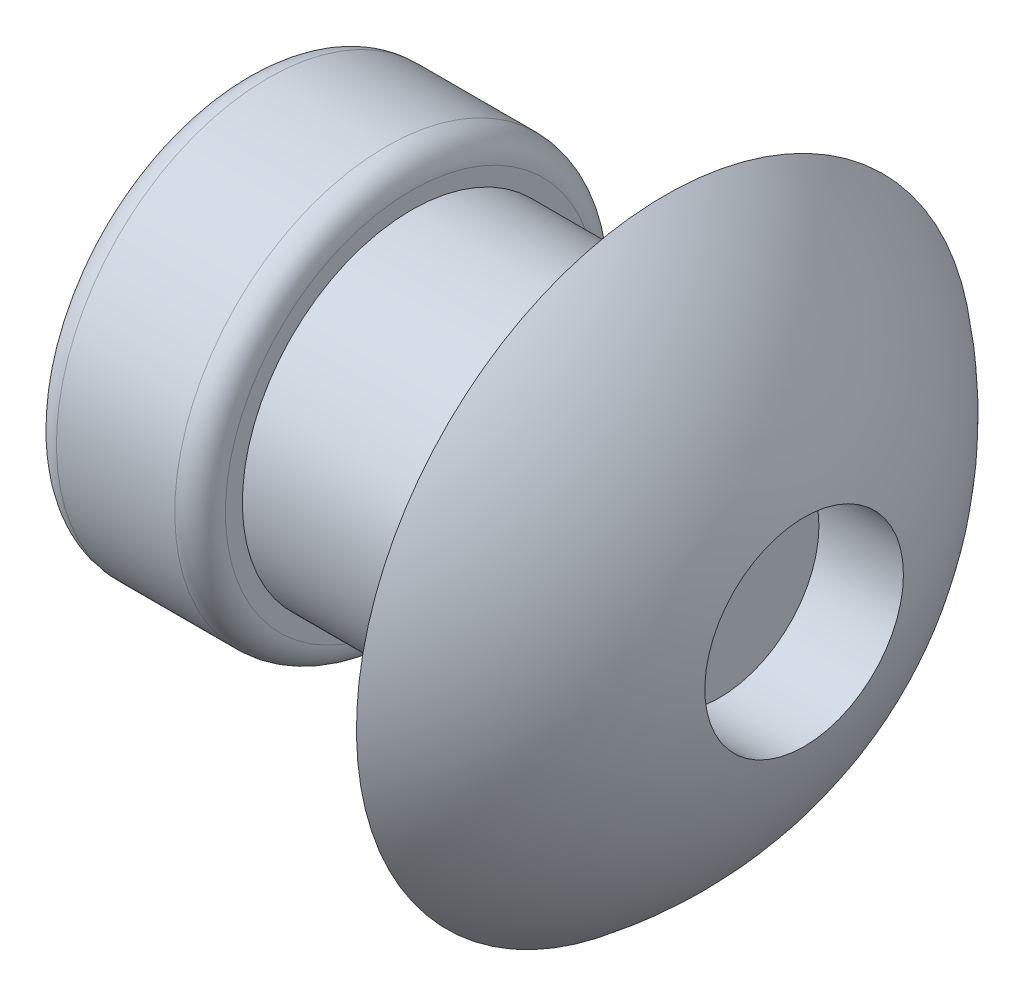
SolidWorks part; units mm, degrees
material "Сталь 20 ГОСТ 1050-88"
ref_plane "Front" through (0, 0, 0) normal (0, 0, 1) x (1, 0, 0)
ref_plane "Top" through (0, 0, 0) normal (0, 1, 0) x (1, 0, 0)
ref_plane "Right" through (0, 0, 0) normal (1, 0, 0) x (0, 0, -1)
sketch "Sketch1" plane through (-11.6035, 14.7235, 0) normal (0, 0, 1) x (0, -1, 0)
  line L0 (16.9235, 12.1035) -> (16.5982, 12.1035)
  line L1 (16.7235, 14.1035) -> (16.7235, 17.1035)
  line L2 (16.7235, 17.1035) -> (18.3735, 17.1035)
  line L3 (14.7235, 33.8377) -> (14.7235, 9.0903) construction
  line L4 (15.8985, 18.7509) -> (15.8985, 46.7509)
  line L5 (15.8985, 46.7509) -> (14.7235, 46.7509)
  line L6 (14.7235, 11.6035) -> (14.7235, 46.7509)
  line L7 (15.8985, 11.6035) -> (14.7235, 11.6035)
  line L8 (16.7235, 14.1035) -> (16.9235, 14.1035)
  line L9 (17.2235, 13.8035) -> (17.2235, 12.4035)
  line L10 (14.7235, 18.9035) -> (13.7235, 18.9035) construction
  arc A0 (18.3735, 17.1035) -> (15.8985, 18.7509) centre (14.7235, 14.3028) ccw
  arc A1 (16.5982, 12.1035) -> (15.8985, 11.6035) centre (15.7235, 12.588) cw
  arc A2 (17.2235, 12.4035) -> (16.9235, 12.1035) centre (16.9235, 12.4035) cw
  arc A3 (16.9235, 14.1035) -> (17.2235, 13.8035) centre (16.9235, 13.8035) cw
  arc A4 (15.8985, 18.7509) -> (14.7235, 18.9035) centre (14.7235, 14.3028) ccw construction
  dimension "D5" = 0.3
  dimension "D2" = 1
  dimension "D4" = 5
  dimension "l" = 3
  dimension "l2" = 2
  dimension "D7" = 0.5
  dimension "K" = 1.8
  dimension "D3" = 1
revolve "Base-Revolve" add sketch "Sketch1" angle 360 about L3
fillet "Fillet1" radius 0.5 1 edges at (5.5, 2, 0)
chamfer "Chamfer1" distance 2.35 angle 15 1 edges at (35.1474, 1.175, 0) first distance on face at (35.1474, 1.175, 0)
sketch "Эскиз1" plane through (0, 0, 0) normal (0, 1, 0) x (1, 0, 0)
  line L0 (35.1474, -0.5453) -> (35.1474, 0.5453) construction
  line L1 (6.1474, 1.175) -> (35.1474, 1.175)
  line L2 (6.1474, 1.175) -> (6.1474, 0)
  line L3 (35.1474, 0) -> (6.1474, 0)
  line L4 (35.1474, 1.175) -> (35.1474, 0)
  line L6 (32.7974, 1.175) -> (7.1474, 1.175) construction
  line L7 (7.1474, -1.175) -> (7.1474, 1.175) construction
  line L8 (35.1474, 0) -> (6.1474, 0) construction
  dimension "D1" = 1
revolve "Вырез-Повернуть1" cut sketch "Эскиз1" angle 360 about L8
sketch "Эскиз2" plane through (0, 0, 0) normal (0, 1, 0) x (1, 0, 0)
  line L0 (2.2, 2.5) -> (0.8, 2.5) construction
  line L1 (-1.5, 2.5) -> (2.5, 2.5)
  line L2 (-1.5, 2.5) -> (-1.5, -2.5)
  line L3 (-1.5, -2.5) -> (2.5, -2.5)
  line L4 (2.5, 2.5) -> (2.5, -2.5)
  line L6 (2.5, -2) -> (2.5, 2) construction
  line L7 (0.8, -2.5) -> (2.2, -2.5) construction
  dimension "D1" = 4
extrude "Вырез-Вытянуть1" [suppressed] cut sketch "Эскиз2" against normal through all both and the other way through all
equation "\"D1@Chamfer1\" = \"d1@Sketch1\""
